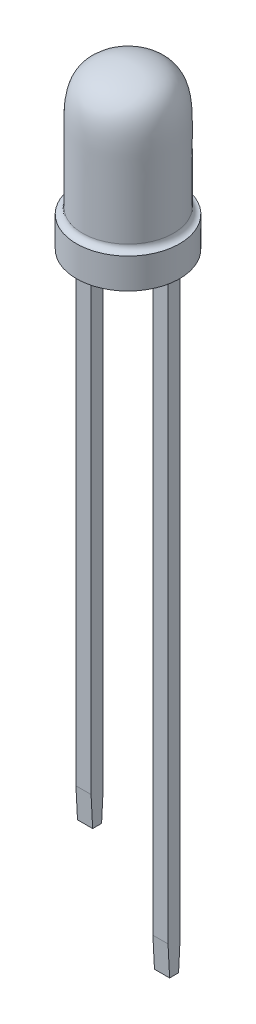
SolidWorks part; units mm, degrees
ref_plane "Front Plane" through (0, 0, 0) normal (0, 0, 1) x (1, 0, 0)
ref_plane "Top Plane" through (0, 0, 0) normal (0, 1, 0) x (1, 0, 0)
ref_plane "Right Plane" through (0, 0, 0) normal (1, 0, 0) x (0, 0, -1)
sketch "Sketch1" plane through (0, 0, 0) normal (0, 0, 1) x (1, 0, 0)
  line L0 (0, 0) -> (0, 5.35)
  line L1 (0, 0) -> (-1.7, 0)
  line L2 (-1.7, 0) -> (-1.7, 1)
  line L3 (-1.7, 1) -> (-1.4999, 1)
  line L4 (0, 5.35) -> (0.8726, 5.35) construction
  line L5 (-1.5, 3.4884) -> (-1.5, 5.2829) construction
  line L6 (-1.4999, 1) -> (-1.4999, 0.624) construction
  spline S0 degree 3 poles (0, 5.35) (-0.2962, 5.35) (-1.4999, 5.1494) (-1.5001, 3.0994) (-1.4999, 1.7555) (-1.4999, 1) knots 0 0 0 0 0.216893 0.523319 1 1 1 1
  dimension "D1" = 5.35
  dimension "D2" = 1.7
  dimension "D3" = 1
  dimension "D4" = 1.5
revolve "Revolve2" add sketch "Sketch1" angle 360 about L0
fillet "Fillet1" radius 0.2 1 edges at (0, 1, -1.4999)
sketch "Sketch2" plane through (0, 0, 0) normal (0, -1, 0) x (1, 0, 0)
  line L0 (0, 0) -> (0, 1.1442) construction
  line L1 (-1.52, -0.2) -> (-1.02, -0.2)
  line L2 (-1.52, -0.2) -> (-1.52, 0.2)
  line L3 (-1.52, 0.2) -> (-1.02, 0.2)
  line L4 (-1.02, -0.2) -> (-1.02, 0.2)
  line L5 (-1.52, -0.2) -> (-1.02, 0.2) construction
  line L6 (-1.52, 0.2) -> (-1.02, -0.2) construction
  line L7 (1.52, 0.2) -> (1.02, -0.2) construction
  line L8 (1.52, -0.2) -> (1.02, 0.2) construction
  line L9 (1.02, -0.2) -> (1.02, 0.2)
  line L10 (1.52, 0.2) -> (1.02, 0.2)
  line L11 (1.52, -0.2) -> (1.52, 0.2)
  line L12 (1.52, -0.2) -> (1.02, -0.2)
  point P0 (-1.27, 0)
  point P12 (1.27, 0)
  dimension "D1" = 0.5
  dimension "D2" = 0.4
  dimension "D3" = 1.27
extrude "Boss-Extrude1" add sketch "Sketch2" along normal blind 17 and the other way blind 0.7 separate body
sketch "Sketch3" plane through (0, -17, 0) normal (0, -1, 0) x (1, 0, 0)
  line L4 (1.52, -0.2) -> (1.52, 0.2)
  line L5 (1.52, 0.2) -> (1.02, 0.2)
  line L6 (1.02, 0.2) -> (1.02, -0.2)
  line L7 (1.02, -0.2) -> (1.52, -0.2)
  line L8 (1.52, -0.2) -> (1.52, 0.2)
  line L9 (1.52, 0.2) -> (1.02, 0.2)
  line L10 (1.02, 0.2) -> (1.02, -0.2)
  line L11 (1.02, -0.2) -> (1.52, -0.2)
  dimension "D1" = 0
extrude "Boss-Extrude2" add sketch "Sketch3" along normal blind 3
chamfer "Chamfer1" distance 1 angle 3 2 edges at (-1.27, -17, -0.2) (-1.27, -17, 0.2) first distance on face at (-1.27, -8.15, -0.2) first distance on face at (-1.27, -8.15, 0.2)
chamfer "Chamfer2" distance 1 angle 3 2 edges at (1.27, -20, -0.2) (1.27, -20, 0.2) first distance on face at (1.27, -9.65, -0.2) first distance on face at (1.27, -9.65, 0.2)
sketch "Sketch4" plane through (0, 0, 0.2) normal (0, 0, 1) x (1, 0, 0)
  line L0 (-1.52, 0.7) -> (-1.52, 0.9)
  line L1 (-1.32, 1.1) -> (-1.27, 1.1)
  line L2 (-1.12, 1.25) -> (-1.12, 2.85)
  line L3 (-1.07, 2.9) -> (0.63, 2.9)
  line L4 (-1.52, 0.7) -> (-1.52, -16)
  line L5 (-1.52, -16) -> (-1.02, -16)
  line L6 (-1.02, -16) -> (-1.02, 0.7)
  line L7 (-1.02, 0.7) -> (-1.52, 0.7)
  line L8 (0.68, 2.85) -> (0.68, 2.5207)
  line L9 (0.6654, 2.4854) -> (-0.1054, 1.7146)
  line L10 (-0.1407, 1.7) -> (-0.67, 1.7)
  line L11 (-0.92, 0.7) -> (-1.52, 0.7)
  line L12 (-0.72, 1.65) -> (-0.72, 0.9)
  line L14 (0.92, 0.7) -> (1.52, 0.7)
  line L15 (1.52, 0.7) -> (1.52, 0.9)
  line L16 (1.32, 1.1) -> (1.27, 1.1)
  line L17 (1.12, 1.25) -> (1.12, 2.85)
  line L18 (1.07, 2.9) -> (0.82, 2.9)
  line L19 (0.77, 2.85) -> (0.77, 2.4707)
  line L20 (0.7554, 2.4354) -> (0.1871, 1.8671)
  line L21 (0.1941, 1.85) -> (0.67, 1.85)
  line L22 (0.72, 1.8) -> (0.72, 0.9)
  line L23 (1.52, 0.7) -> (1.52, -19) construction
  line L24 (1.52, 0.7) -> (1.02, 0.7) construction
  arc A0 (-0.72, 0.9) -> (-0.92, 0.7) centre (-0.92, 0.9) cw
  arc A1 (-1.52, 0.9) -> (-1.32, 1.1) centre (-1.32, 0.9) cw
  arc A2 (-1.27, 1.1) -> (-1.12, 1.25) centre (-1.27, 1.25) ccw
  arc A3 (-0.72, 1.65) -> (-0.67, 1.7) centre (-0.67, 1.65) cw
  arc A4 (-0.1407, 1.7) -> (-0.1054, 1.7146) centre (-0.1407, 1.75) ccw
  arc A5 (0.6654, 2.4854) -> (0.68, 2.5207) centre (0.63, 2.5207) ccw
  arc A6 (0.68, 2.85) -> (0.63, 2.9) centre (0.63, 2.85) ccw
  arc A7 (-1.12, 2.85) -> (-1.07, 2.9) centre (-1.07, 2.85) cw
  arc A8 (0.72, 0.9) -> (0.92, 0.7) centre (0.92, 0.9) ccw
  arc A9 (1.52, 0.9) -> (1.32, 1.1) centre (1.32, 0.9) ccw
  arc A10 (1.27, 1.1) -> (1.12, 1.25) centre (1.27, 1.25) cw
  arc A11 (0.72, 1.8) -> (0.67, 1.85) centre (0.67, 1.8) ccw
  arc A12 (0.7554, 2.4354) -> (0.77, 2.4707) centre (0.72, 2.4707) ccw
  arc A13 (1.12, 2.85) -> (1.07, 2.9) centre (1.07, 2.85) ccw
  arc A14 (0.77, 2.85) -> (0.82, 2.9) centre (0.82, 2.85) cw
  arc A15 (0.1941, 1.85) -> (0.1871, 1.8671) centre (0.1941, 1.86) cw
  point P22 (-0.72, 1.7)
  point P25 (-0.12, 1.7)
  point P30 (0.68, 2.9)
  point P33 (-1.12, 2.9)
  point P49 (1.52, 1.1)
  point P54 (0.72, 1.85)
  point P63 (0.17, 1.85)
  dimension "D10" = 0.2
  dimension "D11" = 0.15
  dimension "D12" = 0.05
  dimension "D20" = 0.2
  dimension "D21" = 0.15
  dimension "D22" = 0.05
  dimension "D23" = 0.01
  dimension "D2" = 1.8
  dimension "D3" = 2.2
  dimension "D4" = 0.4
  dimension "D5" = 0.8
  dimension "D6" = 0.4
  dimension "D7" = 135
  dimension "D8" = 0.6
  dimension "D9" = 0.6
  dimension "D13" = 0.4
  dimension "D14" = 0.4
  dimension "D15" = 0.35
  dimension "D16" = 0.55
  dimension "D17" = 45
  dimension "D18" = 1.15
  dimension "D19" = 0.4
  dimension "D1" = 0
extrude "Boss-Extrude3" add sketch "Sketch4" against normal up to surface (0.4 mm away) separate body up to face at (-1.27, -7.65, -0.2)
combine bodies "Combine1" operation type add bodies to combine 102 106
combine bodies "Combine2" operation type add bodies to combine 107 104
fillet "Fillet2" radius 0.1 1 edges at (-1.02, 0.7, 0)
fillet "Fillet3" radius 0.1 1 edges at (1.02, 0.7, 0)
